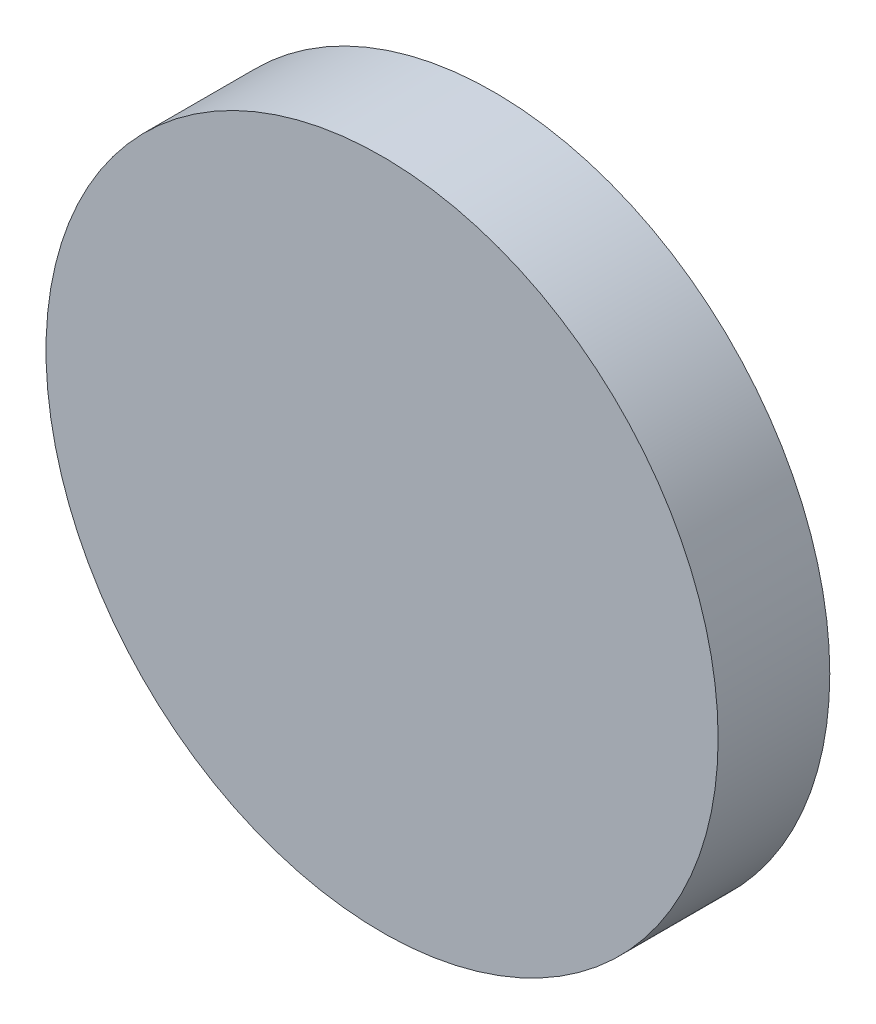
SolidWorks part; units mm, degrees
ref_plane "Спереди" through (0, 0, 0) normal (0, 0, 1) x (1, 0, 0)
ref_plane "Сверху" through (0, 0, 0) normal (0, 1, 0) x (1, 0, 0)
ref_plane "Справа" through (0, 0, 0) normal (1, 0, 0) x (0, 0, -1)
sketch "Sketch1" plane through (0, 0, 0) normal (0, 0, 1) x (1, 0, 0)
  circle A0 centre (0, 0) radius 30.1
  circle A1 centre (0, 0) radius 12.5
  circle A2 centre (0, 12.5) radius 2.5
  circle A3 centre (-9.0136, -8.6605) radius 2.5
  circle A4 centre (9.0136, -8.6605) radius 2.5
  point P0 (0, 12.5)
  point P5 (-9.0136, -8.6605)
  point P6 (9.0136, -8.6605)
  dimension "D1" = 60.2
  dimension "D2" = 25
  dimension "D3" = 5
  dimension "D4" = 5
  dimension "D5" = 5
extrude "Boss-Extrude1" add sketch "Sketch1" along normal blind 10 contours A0
extrude "Boss-Extrude2" add sketch "Sketch1<3>" against normal blind 10 contours A2 | A3 | A4
sketch "Sketch1<3>" plane through (0, 0, 0) normal (0, 0, 1) x (1, 0, 0) same geometry as "Sketch1"
